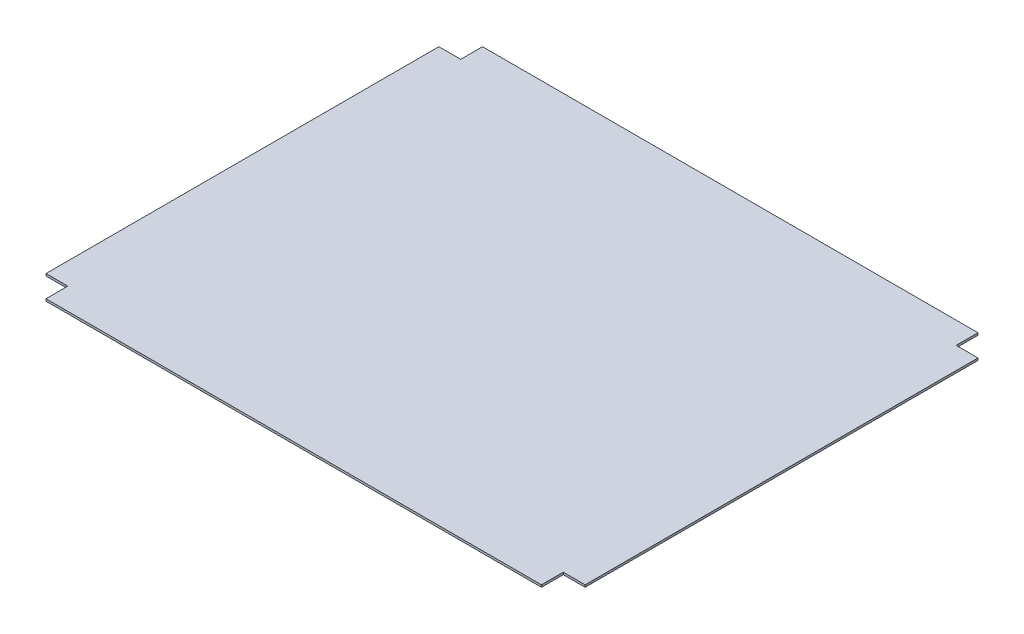
SolidWorks part; units mm, degrees
ref_plane "Ön Düzlem" through (0, 0, 0) normal (0, 0, 1) x (1, 0, 0)
ref_plane "Üst Düzlem" through (0, 0, 0) normal (0, 1, 0) x (1, 0, 0)
ref_plane "Sağ Düzlem" through (0, 0, 0) normal (1, 0, 0) x (0, 0, -1)
sketch "Sketch2" plane through (0, 0, 0) normal (0, 1, 0) x (1, 0, 0)
  line L1 (-247, 0) -> (247, 0)
  line L2 (-247, 0) -> (-247, 400)
  line L3 (-247, 400) -> (247, 400)
  line L4 (247, 0) -> (247, 400)
  point P4 (0, 0)
  dimension "D1" = 494
  dimension "D2" = 400
base flange "Base-Flange1" sketch "Sketch2" thickness 2 reverse thickness direction no parameters "D1"=0.7
sketch "Sketch7" plane through (0, 0, 0) normal (0, 1, 0) x (1, 0, 0)
  line L0 (-247, 200) -> (-378.6198, 200) construction
  line L1 (-247, 400) -> (-227, 400)
  line L2 (-247, 400) -> (-247, 380)
  line L3 (-247, 380) -> (-227, 380)
  line L4 (-227, 400) -> (-227, 380)
  line L5 (-247, 400) -> (-247, 0) construction
  line L6 (0, 400) -> (0, 319.6069) construction
  line L7 (247, 400) -> (-247, 400) construction
  line L8 (-247, 20) -> (-227, 20)
  line L9 (-227, 0) -> (-227, 20)
  line L10 (-247, 0) -> (-227, 0)
  line L11 (-247, 0) -> (-247, 20)
  line L12 (247, 0) -> (247, 20)
  line L13 (247, 0) -> (227, 0)
  line L14 (227, 0) -> (227, 20)
  line L15 (247, 20) -> (227, 20)
  line L16 (227, 400) -> (227, 380)
  line L17 (247, 380) -> (227, 380)
  line L18 (247, 400) -> (247, 380)
  line L19 (247, 400) -> (227, 400)
  dimension "D1" = 20
extrude "Cut-Extrude1" cut sketch "Sketch7" against normal blind 10 normal cut yes
sketch "Büküm-Çizgileri1" [suppressed] plane through (0, 0, 0) normal (0, 1, 0) x (1, 0, 0)
sketch "Sınırlandırma-Kutusu1" [suppressed] plane through (0, 0, 0) normal (0, 1, 0) x (1, 0, 0)
sheet metal parameters "Sac-Levha1" thickness 2 parameters "D1"=0.7
flat pattern "Düz-Çoğaltma1" [suppressed]
sketch "Büküm-Çizgileri2" plane through (0, 0, 0) normal (0, 1, 0) x (1, 0, 0)
sketch3d "Sınırlandırma-Kutusu2" [suppressed]
  line L0 (-453, 400, 0) -> (453, 400, 0) construction
  line L1 (-453, 0, 0) -> (453, 0, 0) construction
  line L2 (-453, 400, 0) -> (-453, 0, 0) construction
  line L3 (453, 400, 0) -> (453, 0, 0) construction
sheet metal parameters "Sac-Levha2" thickness 2 parameters "D1"=0.7
flat pattern "Düz-Çoğaltma1"
sketch "Büküm-Çizgileri2" plane through (0, 0, 0) normal (0, 1, 0) x (1, 0, 0)
sketch3d "Sınırlandırma-Kutusu2" [suppressed]
  line L0 (247, 400, 0) -> (-247, 400, 0) construction
  line L1 (247, 0, 0) -> (-247, 0, 0) construction
  line L2 (247, 400, 0) -> (247, 0, 0) construction
  line L3 (-247, 400, 0) -> (-247, 0, 0) construction
